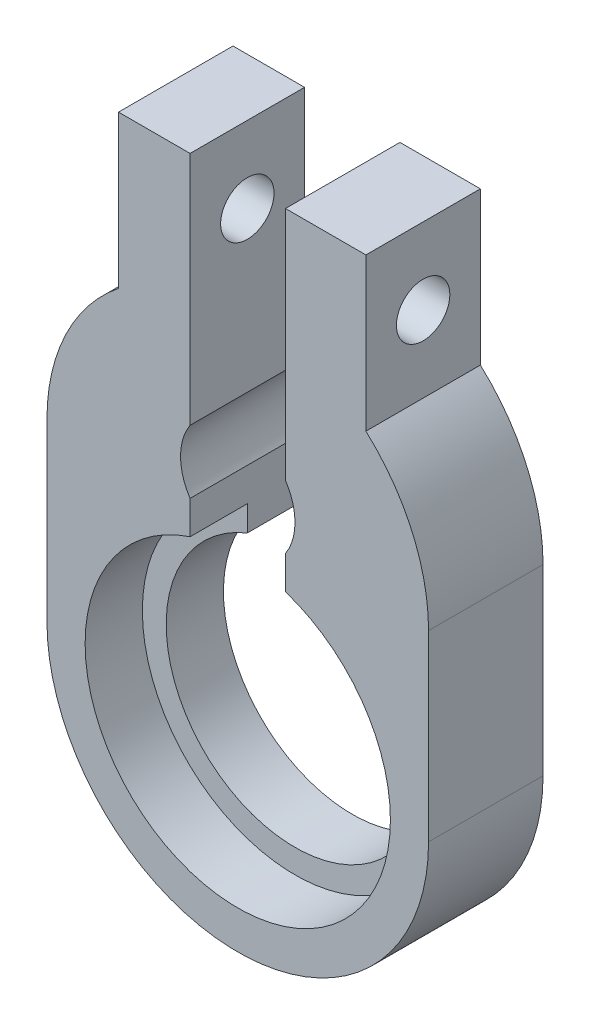
SolidWorks part; units mm, degrees
ref_plane "Front Plane" through (0, 0, 0) normal (1, 0, 0) x (0, 1, 0)
ref_plane "Top Plane" through (0, 0, 0) normal (0, 0, 1) x (0, 1, 0)
ref_plane "Right Plane" through (0, 0, 0) normal (0, 1, 0) x (-1, 0, 0)
sketch "Sketch1" plane through (0, 0, 0) normal (0, 0, 1) x (0, 1, 0)
  line L0 (6.27, 2.5) -> (9.3417, 2.5)
  line L1 (0, 10) -> (17, 10)
  line L2 (25, 6.25) -> (25, 2.5)
  line L3 (17, -10) -> (0, -10)
  line L6 (25, -2.5) -> (25, -6.7156)
  line L7 (12.6583, 2.5) -> (25, 2.5)
  line L8 (12.6583, -2.5) -> (25, -2.5)
  line L11 (25, -6.7156) -> (17, -6.7156)
  line L12 (17, -10) -> (17, -6.7156)
  line L15 (25, 6.25) -> (17, 6.25)
  line L16 (17, 10) -> (17, 6.25)
  line L17 (6.27, -2.5) -> (9.3417, -2.5)
  arc A0 (0, 10) -> (0, -10) centre (0, 0) ccw
  arc A1 (12.6583, 2.5) -> (9.3417, 2.5) centre (11, 0) ccw
  arc A2 (9.3417, -2.5) -> (12.6583, -2.5) centre (11, 0) ccw
  arc A4 (6.27, 2.5) -> (6.27, -2.5) centre (0, 0) ccw
  point P7 (-32.1045, 3.7802)
  point P11 (-19.836, 5.0025)
  point P15 (-10, 0)
  dimension "D2" = 6
  dimension "D3" = 20
  dimension "D6" = 0
  dimension "D4" = 6.75
  dimension "D1" = 21
  dimension "D5" = 5
  dimension "D7" = 35
  dimension "D10" = 5
  dimension "D11" = 10
  dimension "D12" = 10
  dimension "D13" = 3.75
  dimension "D14" = 3.2844
  dimension "D15" = 8
  dimension "D16" = 8
extrude "Boss-Extrude1" add sketch "Sketch1" along normal blind 6
sketch "Sketch2" plane through (10, 0, 0) normal (1, 0, 0) x (0, 1, 0)
  line L0 (25, 6) -> (25, 0) construction
  circle A0 centre (21, 3) radius 1.4
  dimension "D1" = 2.8
  dimension "D2" = 4
extrude "Cut-Extrude1" cut sketch "Sketch2" against normal blind 30
sketch "Sketch3" plane through (0, 0, 6) normal (0, 0, 1) x (1, 0, 0)
  circle A0 centre (0, 0) radius 8
  dimension "D1" = 16
extrude "Cut-Extrude2" cut sketch "Sketch3" against normal blind 3
fillet "Fillet1" radius 10 1 edges at (10, 17, 3)
fillet "Fillet2" radius 10 1 edges at (-10, 17, 3)
